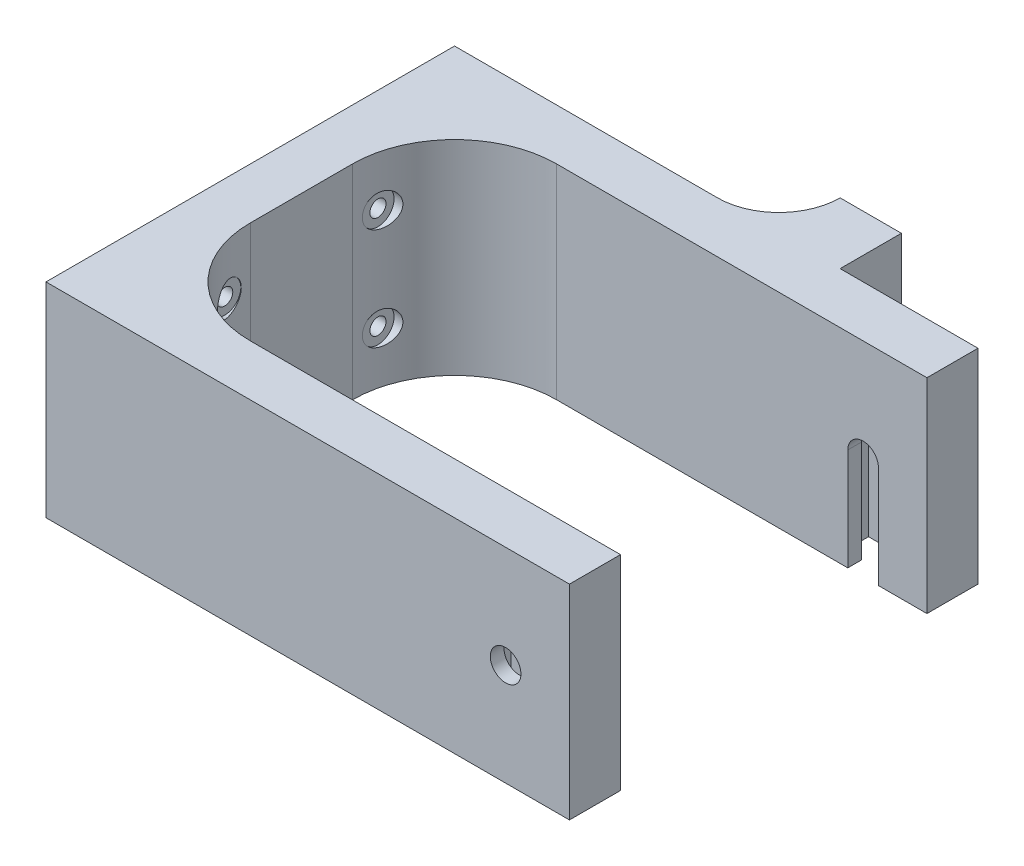
SolidWorks part; units mm, degrees
material "6061-T6 (SS)"
ref_plane "Front Plane" through (0, 0, 0) normal (0, 0, 1) x (1, 0, 0)
ref_plane "Top Plane" through (0, 0, 0) normal (0, 1, 0) x (1, 0, 0)
ref_plane "Right Plane" through (0, 0, 0) normal (1, 0, 0) x (0, 0, -1)
ref_plane "Plane1" through (0, 0, 50.8) normal (0, 0, 1) x (1, 0, 0)
sketch "Sketch1" plane through (0, 0, 50.8) normal (0, 0, 1) x (1, 0, 0)
  line L1 (0, 0) -> (101.6, 0) construction
  line L4 (101.6, 15.875) -> (101.6, -15.875) construction
  line L5 (0, 25.4) -> (-12.7, 25.4)
  line L6 (-12.7, 25.4) -> (-12.7, -25.4)
  line L7 (-12.7, -25.4) -> (0, -25.4)
  line L8 (0, -25.4) -> (117.475, -25.4)
  line L9 (117.475, 0) -> (117.475, -25.4)
  line L10 (117.475, 0) -> (117.475, 25.4)
  line L11 (117.475, 25.4) -> (0, 25.4)
  circle A0 centre (101.6, 0) radius 3.81
  arc A1 (101.6, -15.875) -> (101.6, 15.875) centre (101.6, 0) ccw construction
  point P1 (-12.7, 0)
  point P4 (0, 0)
  dimension "D3" = 7.62
  dimension "D4" = 15.875
  dimension "D1" = 50.8
  dimension "D2" = 101.6
  dimension "D5" = 12.7
  dimension "D6" = 12.7
extrude "Boss-Extrude1" add sketch "Sketch1" along normal blind 101.6
sketch "Sketch2" plane through (0, 0, 0) normal (0, 0, 1) x (1, 0, 0)
  line L0 (0, 25.4) -> (0, -25.4) construction
  point P3 (0, 0)
  dimension "D1" = 50.8
sketch "Sketch3" plane through (0, 0, 152.4) normal (0, 0, 1) x (1, 0, 0)
  line L1 (0, -25.4) -> (0, 25.4)
  line L5 (-12.7, 25.4) -> (-12.7, -25.4)
  line L6 (-12.7, -25.4) -> (117.475, -25.4)
  line L7 (117.475, -25.4) -> (117.475, 25.4)
  line L9 (117.475, 25.4) -> (-12.7, 25.4)
  line L16 (0, -25.4) -> (117.475, -25.4)
  line L17 (117.475, -25.4) -> (117.475, 25.4)
  line L22 (117.475, 25.4) -> (0, 25.4)
  point P7 (0, 0)
  dimension "D1" = 0
extrude "Cut-Extrude1" cut sketch "Sketch3" against normal blind 76.2 from offset 12.7 offset against normal yes
fillet "Fillet1" radius 25.4 2 edges at (0, 0, 63.5) (0, 0, 139.7)
sketch "Sketch4" plane through (0, 0, 50.8) normal (0, 0, -1) x (-1, 0, 0)
  line L3 (-97.79, 0) -> (-97.79, -25.4)
  line L4 (-105.41, 0) -> (-105.41, -25.4)
  line L5 (-97.79, -25.4) -> (-105.41, -25.4)
  line L6 (12.7, -25.4) -> (-117.475, -25.4) construction
  circle A0 centre (-101.6, 0) radius 3.81 construction
  arc A2 (-97.79, 0) -> (-105.41, 0) centre (-101.6, 0) ccw
  point P7 (0, 0)
sketch "Sketch5" plane through (0, 0, 0) normal (0, 1, 0) x (1, 0, 0)
  line L0 (105.41, -50.8) -> (97.79, -50.8) construction
  line L1 (105.41, -50.8) -> (97.79, -50.8) construction
  line L2 (105.41, -50.8) -> (113.284, -50.8) construction
  line L3 (113.284, -50.8) -> (113.284, -57.15) construction
  line L4 (113.284, -57.15) -> (115.284, -57.15) construction
  circle A0 centre (115.284, -57.15) radius 2
  dimension "D3" = 4
  dimension "D1" = 15.494
  dimension "D2" = 6.35
sketch "Sketch6" plane through (-12.7, 0, 0) normal (-1, 0, 0) x (0, 0, 1)
  line L1 (152.4, -25.4) -> (50.8, -25.4) construction
  line L2 (152.4, 25.4) -> (50.8, 25.4) construction
  line L6 (88.9, -25.4) -> (114.3, -25.4)
  line L7 (88.9, 25.4) -> (88.9, -25.4)
  line L8 (114.3, 25.4) -> (88.9, 25.4)
  line L9 (114.3, -25.4) -> (114.3, 25.4)
  line L13 (88.9, -25.4) -> (114.3, -25.4) construction
  line L14 (88.9, 25.4) -> (88.9, -25.4) construction
  line L15 (114.3, 25.4) -> (88.9, 25.4) construction
  line L16 (114.3, -25.4) -> (114.3, 25.4) construction
  circle A0 centre (120.65, -12.7) radius 2
  circle A1 centre (120.65, 12.7) radius 2
  circle A2 centre (82.55, 12.7) radius 2
  circle A3 centre (82.55, -12.7) radius 2
  dimension "D1" = 4
  dimension "D3" = 6.35
  dimension "D4" = 6.35
  dimension "D5" = 12.7
  dimension "D6" = 12.7
  dimension "D2" = 0
extrude "Cut-Extrude4" cut sketch "Sketch6" against normal through all
sketch "Sketch7" plane through (-12.7, 0, 0) normal (-1, 0, 0) x (0, 0, 1)
  circle A0 centre (120.65, 12.7) radius 4
  circle A1 centre (82.55, -12.7) radius 2
  circle A2 centre (82.55, -12.7) radius 2 construction
  circle A3 centre (82.55, 12.7) radius 2
  circle A4 centre (82.55, 12.7) radius 2 construction
  circle A5 centre (120.65, 12.7) radius 2
  circle A6 centre (120.65, 12.7) radius 2 construction
  circle A7 centre (120.65, -12.7) radius 2
  circle A8 centre (120.65, -12.7) radius 2 construction
  circle A9 centre (120.65, -12.7) radius 4
  circle A10 centre (82.55, 12.7) radius 4
  circle A11 centre (82.55, -12.7) radius 4
  dimension "D5" = 8
  dimension "D1" = 0
  dimension "D2" = 0
  dimension "D3" = 0
  dimension "D4" = 0
extrude "Cut-Extrude5" cut sketch "Sketch7" against normal through all from offset 12.7 offset against normal yes
sketch "Sketch8" plane through (0, 0, 50.8) normal (0, 0, -1) x (-1, 0, 0)
  line L0 (-83.185, -19.05) -> (-83.185, 19.05)
  line L1 (-83.185, -19.05) -> (-67.945, -19.05)
  line L3 (-83.185, 19.05) -> (-67.945, 19.05)
  line L5 (-67.945, 19.05) -> (-67.945, -19.05)
  circle A2 centre (-101.6, 0) radius 3.175 construction
  circle A3 centre (-101.6, 0) radius 3.81 construction
  circle A4 centre (-101.6, 0) radius 3.81 construction
  point P6 (-83.185, 0)
  point P7 (-98.425, 0)
  dimension "D1" = 6.35
  dimension "D2" = 38.1
  dimension "D3" = 15.24
  dimension "D4" = 15.24
extrude "Boss-Extrude2" add sketch "Sketch8" along normal blind 15.24
ref_plane "Plane2" through (0, 0, 146.05) normal (0, 0, -1) x (-1, 0, 0)
sketch "Sketch9" plane through (0, 0, 146.05) normal (0, 0, -1) x (-1, 0, 0)
  circle A0 centre (-101.6, 0) radius 3.81 construction
  circle A1 centre (-101.6, 0) radius 3.81 construction
  circle A2 centre (-101.6, 0) radius 7.9375
  dimension "D1" = 15.875
extrude "Cut-Extrude6" cut sketch "Sketch9" against normal mid plane 5.88
sketch "Sketch10" plane through (0, 0, 0) normal (0, 1, 0) x (1, 0, 0)
  line L0 (109.5375, -148.99) -> (109.5375, -143.11)
  line L1 (93.6625, -143.11) -> (93.6625, -148.99)
  line L4 (93.6625, -143.11) -> (109.5375, -143.11)
  line L5 (109.5375, -148.99) -> (93.6625, -148.99)
  line L8 (93.6625, -143.11) -> (93.6625, -148.99)
  line L9 (109.5375, -148.99) -> (109.5375, -143.11)
  dimension "D1" = 15.875
extrude "Cut-Extrude8" cut sketch "Sketch10" against normal through all
ref_plane "Plane3" through (0, 0, 101.6) normal (0, 0, 1) x (1, 0, 0)
mirror "Mirror1" about plane through (0, 0, 101.6) normal (0, 0, 1) of "Cut-Extrude8", "Cut-Extrude6"
fillet "Fillet2" radius 15.24 1 edges at (67.945, 0, 50.8)
extrude "Cut-Extrude10" cut sketch "Sketch4" against normal up to surface (12.7 mm away) up to face at (105.41, 0, 63.5)
sketch "Sketch13" plane through (0, 19.05, 0) normal (0, 1, 0) x (1, 0, 0)
  line L3 (52.705, -50.8) -> (83.185, -50.8)
  line L4 (83.185, -50.8) -> (83.185, -35.56)
  line L5 (83.185, -35.56) -> (67.945, -35.56)
  line L6 (52.705, -50.8) -> (83.185, -50.8)
  line L7 (83.185, -50.8) -> (83.185, -35.56)
  line L8 (83.185, -35.56) -> (67.945, -35.56)
  arc A1 (52.705, -50.8) -> (67.945, -35.56) centre (52.705, -35.56) ccw
  arc A2 (52.705, -50.8) -> (67.945, -35.56) centre (52.705, -35.56) ccw
  dimension "D1" = 0
extrude "Boss-Extrude3" add sketch "Sketch13" along normal up to surface (6.35 mm away) up to face at (48.4779, 25.4, 101.6)
sketch "Sketch14" plane through (83.185, 0, 0) normal (1, 0, 0) x (0, 0, -1)
  line L0 (-44.4564, -14.2812) -> (-44.4564, 14.2812) construction
  line L3 (-50.8, 25.4) -> (-50.8, -19.05) construction
  circle A0 centre (-44.4564, -14.2812) radius 1.8986
  circle A1 centre (-44.4564, 14.2812) radius 1.8986
  point P4 (-44.4564, -12.3825)
  point P5 (-44.4564, 12.3825)
  point P6 (-44.4564, 0)
  dimension "D1" = 3.7973
  dimension "D2" = 24.765
  dimension "D3" = 6.3436
extrude "Cut-Extrude11" cut sketch "Sketch14" against normal through all
sketch "Sketch15" plane through (83.185, 0, 0) normal (1, 0, 0) x (0, 0, -1)
  circle A0 centre (-44.4564, 14.2812) radius 1.8987 construction
  circle A1 centre (-44.4564, -14.2812) radius 1.8987 construction
  circle A2 centre (-44.4564, 14.2812) radius 1.8986 construction
  circle A3 centre (-44.4564, -14.2812) radius 1.8986 construction
equation "\"HeightOfTubing\"=2"
equation "\"D1@Sketch1\"=\"HeightOfTubing\""
equation "\"D1@Sketch2\"=\"HeightOfTubing\""
